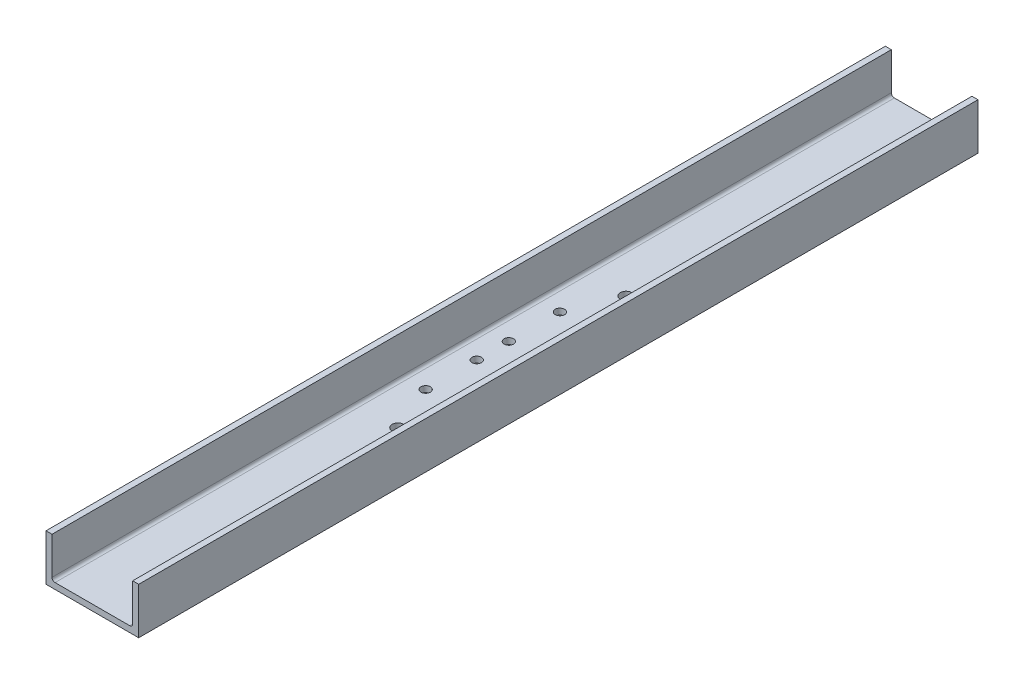
SolidWorks part; units mm, degrees
ref_plane "Front Plane" through (0, 0, 0) normal (0, 0, 1) x (1, 0, 0)
ref_plane "Top Plane" through (0, 0, 0) normal (0, 1, 0) x (1, 0, 0)
ref_plane "Right Plane" through (0, 0, 0) normal (1, 0, 0) x (0, 0, -1)
sketch "Sketch1" plane through (0, 0, 0) normal (0, 0, 1) x (1, 0, 0)
  line L0 (-25.4, 12.7) -> (-25.4, -12.7) construction
  line L1 (-25.4, -12.7) -> (25.4, -12.7) construction
  line L2 (25.4, -12.7) -> (25.4, 12.7) construction
  line L3 (22.098, -9.398) -> (-22.098, -9.398) construction
  line L4 (-22.098, -9.398) -> (-22.098, 12.7) construction
  line L6 (-22.098, 12.7) -> (-25.4, 12.7) construction
  line L7 (0, -12.7) -> (0, 0) construction
  line L8 (25.4, 12.7) -> (22.098, 12.7) construction
  line L9 (22.098, 12.7) -> (22.098, -9.398) construction
  line L10 (0, -9.398) -> (0, -12.7) construction
  point P4 (0, 0)
  point P11 (25.4, -9.398)
  dimension "Outside Height" = 25.4
  dimension "Outside Width" = 50.8
  dimension "Leg Thickness" = 3.302
  dimension "D1" = 12.7
  dimension "Inside Height" = 22.098
  dimension "Inside Width" = 44.196
  dimension "Base Thickness" = 3.302
sketch "Sketch2" plane through (0, 0, 0) normal (1, 0, 0) x (0, 0, -1)
  line L0 (230, 12.7) -> (-230, 12.7) construction
  line L1 (0, -9.398) -> (0, 12.7) construction
  point P0 (-179.2, 12.7)
  point P4 (0, 12.7)
  point P6 (179.2, 12.7)
  dimension "D1" = 50.8
  dimension "D2" = 50.8
  dimension "Length" = 460
sketch "Sketch3" plane through (0, 0, 0) normal (0, 0, 1) x (1, 0, 0)
  line L6 (-25.4, 12.7) -> (-25.4, -12.7)
  line L7 (-25.4, -12.7) -> (25.4, -12.7)
  line L8 (25.4, -12.7) -> (25.4, 12.7)
  line L9 (25.4, 12.7) -> (22.098, 12.7)
  line L10 (22.098, 12.7) -> (22.098, -9.398)
  line L11 (22.098, -9.398) -> (-22.098, -9.398)
  line L12 (-22.098, -9.398) -> (-22.098, 12.7)
  line L13 (-22.098, 12.7) -> (-25.4, 12.7)
extrude "Boss-Extrude1" add sketch "Sketch3" along normal mid plane 460
fillet "Fillet1" radius 1.651 2 edges at (22.098, -9.398, 0) (-22.098, -9.398, 0)
sketch "Sketch4" plane through (0, -9.398, 0) normal (0, 1, 0) x (1, 0, 0)
  line L0 (0, 230) -> (0, -230) construction
  line L1 (20.447, 230) -> (-20.447, 230) construction
  line L2 (20.447, -230) -> (-20.447, -230) construction
  line L3 (-23.5304, 0) -> (23.5304, 0) construction
  circle A0 centre (-10.5304, 8.79) radius 2.585
  circle A1 centre (10.4696, 8.79) radius 2.585
  circle A2 centre (-10.5304, 36.79) radius 2.585
  circle A3 centre (10.4696, 36.79) radius 2.585
  circle A4 centre (-10.5304, -36.79) radius 2.585
  circle A5 centre (10.4696, -36.79) radius 2.585
  circle A6 centre (10.4696, -8.79) radius 2.585
  circle A7 centre (-10.5304, -8.79) radius 2.585
  point P24 (0, 0)
  point P26 (0, 0)
  dimension "D1" = 5.17
  dimension "D2" = 5.17
  dimension "D3" = 28
  dimension "D4" = 8.79
  dimension "D5" = 8.79
  dimension "D6" = 28
extrude "Cut-Extrude1" cut sketch "Sketch4" against normal blind 10
sketch "Sketch5" plane through (0, -9.398, 0) normal (0, 1, 0) x (1, 0, 0)
  circle A0 centre (0, 62.5214) radius 3.18
  circle A2 centre (0, -62.52) radius 3.18
  circle A3 centre (-10.5304, -8.79) radius 2.585 construction
  dimension "D1" = 53.73
extrude "Cut-Extrude2" cut sketch "Sketch5" against normal through all
equation "\"D1@Boss-Extrude1\"=\"Length@Sketch2\""
equation "\"D2@Sketch2\"=\"D1@Sketch2\""
equation "\"D1@Sketch1\"=\"Outside Height@Sketch1\"/2"
equation "\"D1@Fillet1\"=\"Leg Thickness@Sketch1\"*.5"
equation "\"D1@Sketch2\"=\"Outside Width@Sketch1\"*1"
